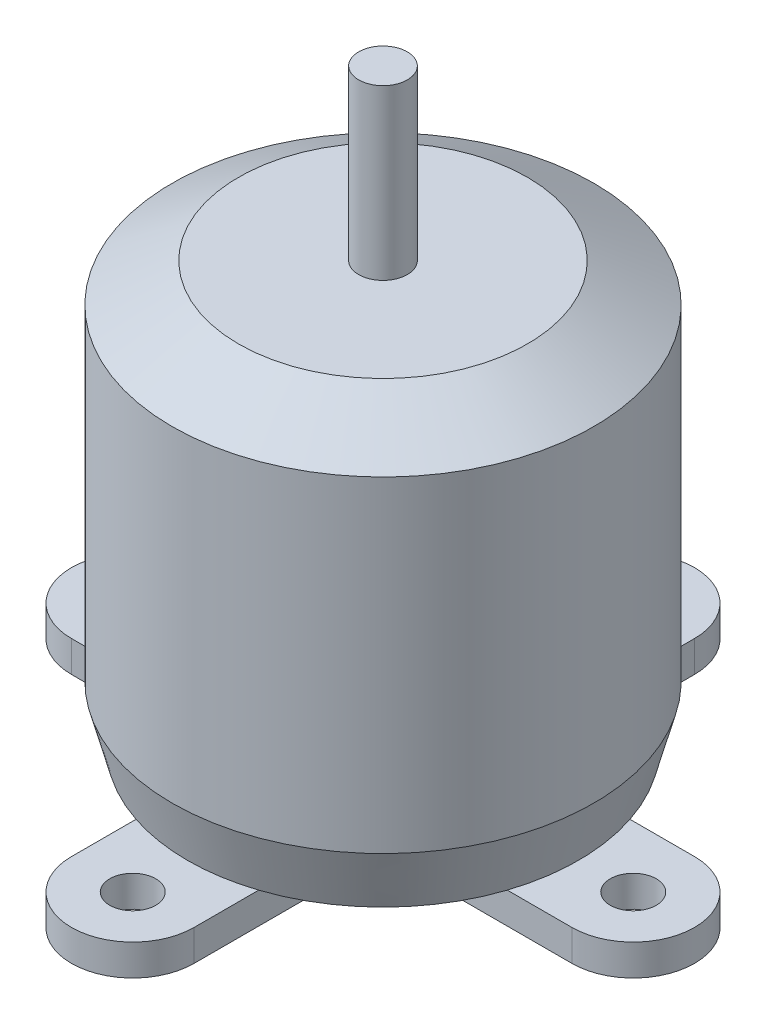
SolidWorks part; units mm, degrees
ref_plane "Front Plane" through (0, 0, 0) normal (0, 0, 1) x (1, 0, 0)
ref_plane "Top Plane" through (0, 0, 0) normal (0, 1, 0) x (1, 0, 0)
ref_plane "Right Plane" through (0, 0, 0) normal (1, 0, 0) x (0, 0, -1)
sketch "Sketch1" plane through (0, 0, 0) normal (0, 1, 0) x (1, 0, 0)
  circle A0 centre (0, 0) radius 13.75
  dimension "D1" = 27.5
extrude "Boss-Extrude1" add sketch "Sketch1" along normal blind 27.5
sketch "Sketch3" plane through (0, 27.5, 0) normal (0, 1, 0) x (1, 0, 0)
  circle A0 centre (0, 0) radius 1.585
  dimension "D1" = 3.17
extrude "Boss-Extrude2" add sketch "Sketch3" along normal blind 11
chamfer "Chamfer1" distance 2.5 angle 60 1 edges at (0, 27.5, 13.75) first distance on face at (0, 27.5, 13.75)
chamfer "Chamfer2" distance 1 angle 75 1 edges at (0, 0, 13.75) first distance on face at (0, 0, 13.75)
sketch "Sketch4" plane through (0, 0, 0) normal (0, -1, 0) x (1, 0, 0)
  line L0 (0, 12.32) -> (0, 20.32) construction
  line L1 (0, -54.6947) -> (0, 54.6947) construction
  line L2 (4, 16.32) -> (4, 9)
  line L3 (-4, 16.32) -> (-4, 9)
  line L4 (-4, 4) -> (0, 0) construction
  line L5 (0, 0) -> (4, 4) construction
  line L6 (15.125, 0) -> (-15.125, 0) construction
  line L7 (16.32, -4) -> (9, -4)
  line L8 (16.32, 4) -> (9, 4)
  line L9 (-4, -16.32) -> (-4, -9)
  line L10 (4, -16.32) -> (4, -9)
  line L11 (-16.32, 4) -> (-9, 4)
  line L12 (-16.32, -4) -> (-9, -4)
  arc A0 (4, 16.32) -> (-4, 16.32) centre (0, 16.32) ccw
  circle A1 centre (0, 16.32) radius 1.5
  arc A2 (16.32, -4) -> (16.32, 4) centre (16.32, 0) ccw
  circle A3 centre (16.32, 0) radius 1.5
  arc A4 (-4, -16.32) -> (4, -16.32) centre (0, -16.32) ccw
  circle A5 centre (0, -16.32) radius 1.5
  arc A6 (-16.32, 4) -> (-16.32, -4) centre (-16.32, 0) ccw
  circle A7 centre (-16.32, 0) radius 1.5
  arc A8 (9, 4) -> (4, 9) centre (9, 9) cw
  arc A9 (-9, 4) -> (-4, 9) centre (-9, 9) ccw
  arc A10 (-4, -9) -> (-9, -4) centre (-9, -9) ccw
  arc A11 (9, -4) -> (4, -9) centre (9, -9) ccw
  point P5 (0, 16.32)
  point P36 (0, 0)
  dimension "D3" = 3
  dimension "D6" = 5
  dimension "D7" = 5
  dimension "D8" = 5
  dimension "D9" = 5
  dimension "D1" = 20.32
  dimension "D2" = 4
  dimension "D4" = 45
  dimension "D5" = 4
extrude "Boss-Extrude3" add sketch "Sketch4" along normal blind 2.032
